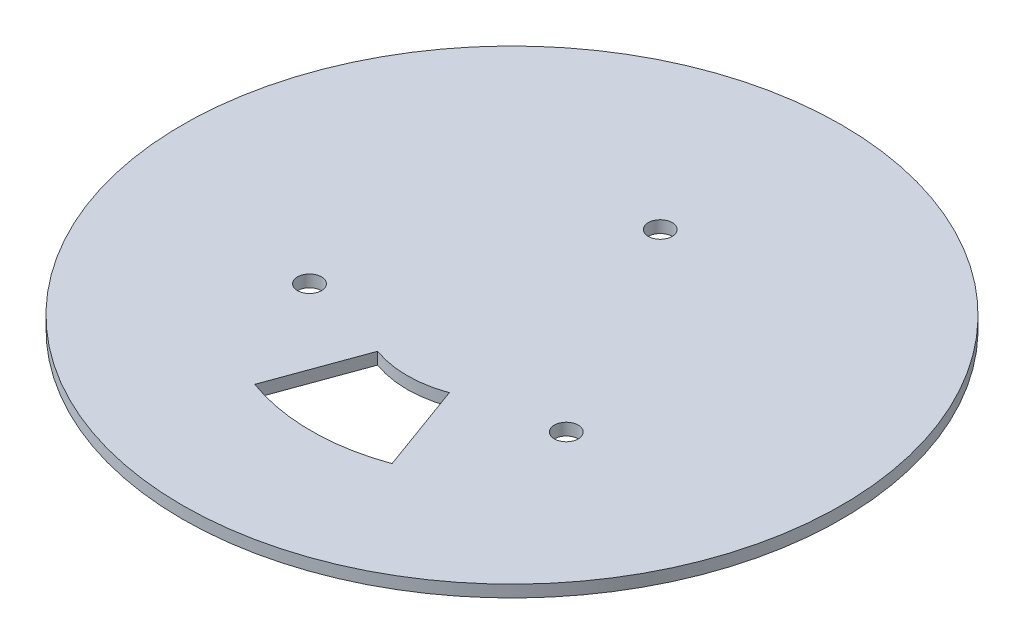
SolidWorks part; units mm, degrees
ref_plane "Plano frontal" through (0, 0, 0) normal (0, 0, 1) x (1, 0, 0)
ref_plane "Plano superior" through (0, 0, 0) normal (0, 1, 0) x (1, 0, 0)
ref_plane "Plano direito" through (0, 0, 0) normal (1, 0, 0) x (0, 0, -1)
sketch "Esboço1" plane through (0, 0, 0) normal (0, 1, 0) x (1, 0, 0)
  circle A0 centre (0, 0) radius 110
extrude "Ressalto-extrusão1" add sketch "Esboço1" along normal blind 4
sketch "Esboço2" plane through (0, 4, 0) normal (0, 1, 0) x (1, 0, 0)
  line L0 (-11.9707, -32.8892) -> (-22.9153, -62.9594) construction
  line L1 (11.9707, -32.8892) -> (22.9153, -62.9594) construction
  line L2 (-11.9707, -32.8892) -> (-22.9153, -62.9594)
  line L3 (11.9707, -32.8892) -> (22.9153, -62.9594)
  arc A0 (-22.9153, -62.9594) -> (22.9153, -62.9594) centre (0, 0) ccw construction
  arc A1 (-11.9707, -32.8892) -> (11.9707, -32.8892) centre (0, 0) ccw construction
  arc A2 (-22.9153, -62.9594) -> (22.9153, -62.9594) centre (0, 0) ccw
  arc A3 (-11.9707, -32.8892) -> (11.9707, -32.8892) centre (0, 0) ccw
extrude "Corte-extrusão1" cut sketch "Esboço2" against normal through all
sketch "Esboço3" plane through (0, 4, 0) normal (0, 1, 0) x (1, 0, 0)
  circle A0 centre (42.8509, -24.74) radius 4 construction
  circle A1 centre (0, 49.48) radius 4 construction
  circle A2 centre (-42.8509, -24.74) radius 4 construction
  circle A3 centre (42.8509, -24.74) radius 4
  circle A4 centre (0, 49.48) radius 4
  circle A5 centre (-42.8509, -24.74) radius 4
extrude "Corte-extrusão2" cut sketch "Esboço3" against normal through all
